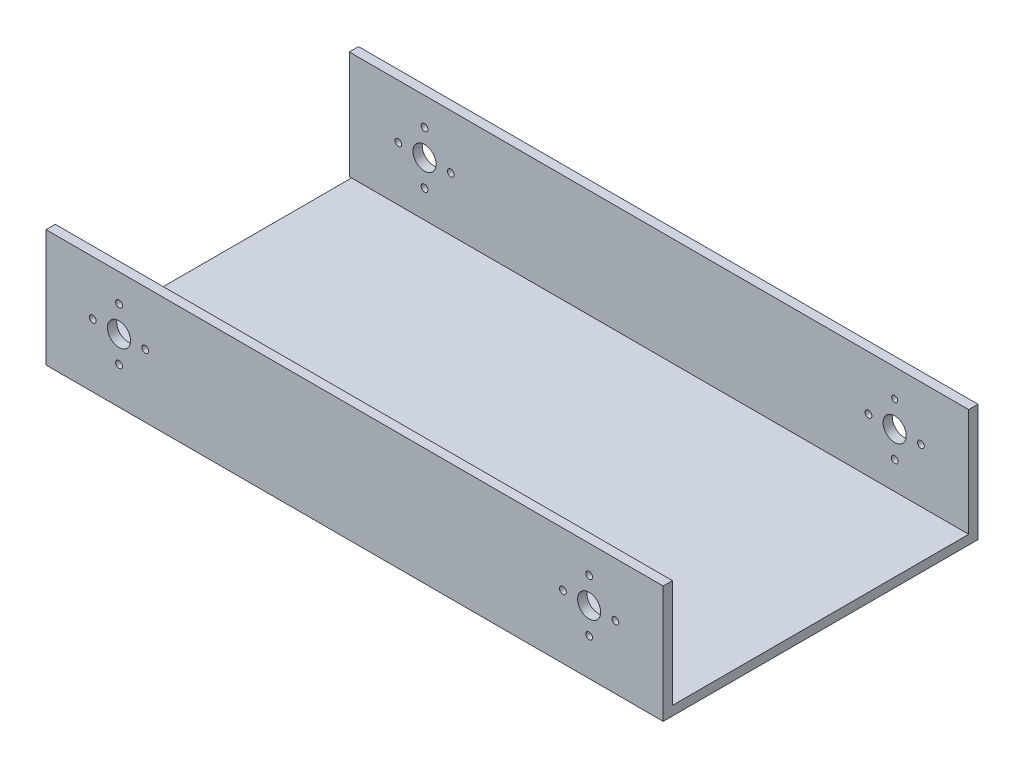
SolidWorks part; units mm, degrees
ref_plane "Front Plane" through (0, 0, 0) normal (0, 0, 1) x (1, 0, 0)
ref_plane "Top Plane" through (0, 0, 0) normal (0, 1, 0) x (1, 0, 0)
ref_plane "Right Plane" through (0, 0, 0) normal (1, 0, 0) x (0, 0, -1)
sketch "스케치1" plane through (0, 0, 0) normal (0, 0, 1) x (1, 0, 0)
  line L1 (-100, 17.5) -> (100, 17.5)
  line L2 (-100, 17.5) -> (-100, -17.5)
  line L3 (-100, -17.5) -> (100, -17.5)
  line L4 (100, 17.5) -> (100, -17.5)
  dimension "D1" = 17.5
  dimension "D2" = 35
  dimension "D3" = 100
  dimension "D4" = 200
extrude "보스-돌출1" add sketch "스케치1" along normal blind 3
sketch "스케치2" plane through (0, 0, 3) normal (0, 0, 1) x (1, 0, 0)
  line L0 (0, 0) -> (50000, 0) construction
  line L1 (0, 0) -> (0, -50000) construction
  line L2 (-76, 0) -> (-76, -50000) construction
  line L3 (76, 0) -> (76, -50000) construction
  circle A0 centre (-76.34, 0) radius 3.75
  circle A1 centre (76, 0) radius 3.75
  dimension "D1" = 76
  dimension "D2" = 76
extrude "컷-돌출1" cut sketch "스케치2" against normal blind 3
sketch "스케치3" plane through (0, 0, 3) normal (0, 0, 1) x (1, 0, 0)
  line L0 (-76.34, 0) -> (-76.34, 50000) construction
  line L1 (76, 0) -> (76, 50000) construction
  line L2 (-76.34, 0) -> (49923.66, 0) construction
  circle A0 centre (-76.34, 0) radius 8.5 construction
  circle A1 centre (76, 0) radius 8.5 construction
  circle A2 centre (-76.34, 8.5) radius 1.1
  circle A3 centre (-76.34, -8.5) radius 1.1
  circle A4 centre (-84.84, 0) radius 1.1
  circle A5 centre (-67.84, 0) radius 1.1
  circle A6 centre (76, 8.5) radius 1.1
  circle A7 centre (76, -8.5) radius 1.1
  circle A8 centre (67.5, 0) radius 1.1
  circle A9 centre (84.5, 0) radius 1.1
extrude "컷-돌출2" cut sketch "스케치3" against normal blind 3
sketch "스케치4" plane through (0, -17.5, 0) normal (0, -1, 0) x (1, 0, 0)
  line L0 (-100, 0) -> (-100, 50000) construction
  line L1 (100, 0) -> (100, 50000) construction
  line L2 (-100, 3) -> (49900, 3) construction
  line L6 (-100, -96) -> (49900, -96) construction
  line L7 (-100, -99) -> (49900, -99) construction
  line L8 (-100, 0) -> (49900, 0) construction
  line L11 (100, 3) -> (-100, 3)
  line L12 (100, 3) -> (100, -99)
  line L13 (100, -99) -> (-100, -99)
  line L14 (-100, 3) -> (-100, -99)
  dimension "D1" = 3
  dimension "D2" = 96
extrude "보스-돌출2" add sketch "스케치4" along normal blind 3
sketch "스케치5" plane through (0, -17.5, 0) normal (0, 1, 0) x (1, 0, 0)
  line L0 (-100, 99) -> (49900, 99) construction
  line L1 (86.532, 96) -> (50086.532, 96) construction
  line L2 (-100, 0) -> (-100, 50000) construction
  line L4 (100, 0) -> (100, 50000) construction
  line L7 (-100.7209, 99) -> (100, 99)
  line L8 (-100.7209, 99) -> (-100.7209, 96)
  line L9 (-100.7209, 96) -> (100, 96)
  line L10 (100, 99) -> (100, 96)
  dimension "D1" = 3
extrude "보스-돌출3" add sketch "스케치5" along normal blind 35
sketch "스케치6" plane through (0, 0, -99) normal (0, 0, -1) x (-1, 0, 0)
  circle A0 centre (-76, 0) radius 3.75
  circle A1 centre (76.34, 0) radius 3.75
  circle A2 centre (-76, -8.5) radius 1.1
  circle A3 centre (-67.5, 0) radius 1.1
  circle A4 centre (-76, 8.5) radius 0.9817
  circle A5 centre (-84.5, 0) radius 1.1
  circle A6 centre (84.84, 0) radius 1.1
  circle A7 centre (76.34, 8.5) radius 1.1
  circle A8 centre (67.84, 0) radius 1.1
  circle A9 centre (76.34, -8.5) radius 1.1
extrude "컷-돌출3" cut sketch "스케치6" against normal blind 35
